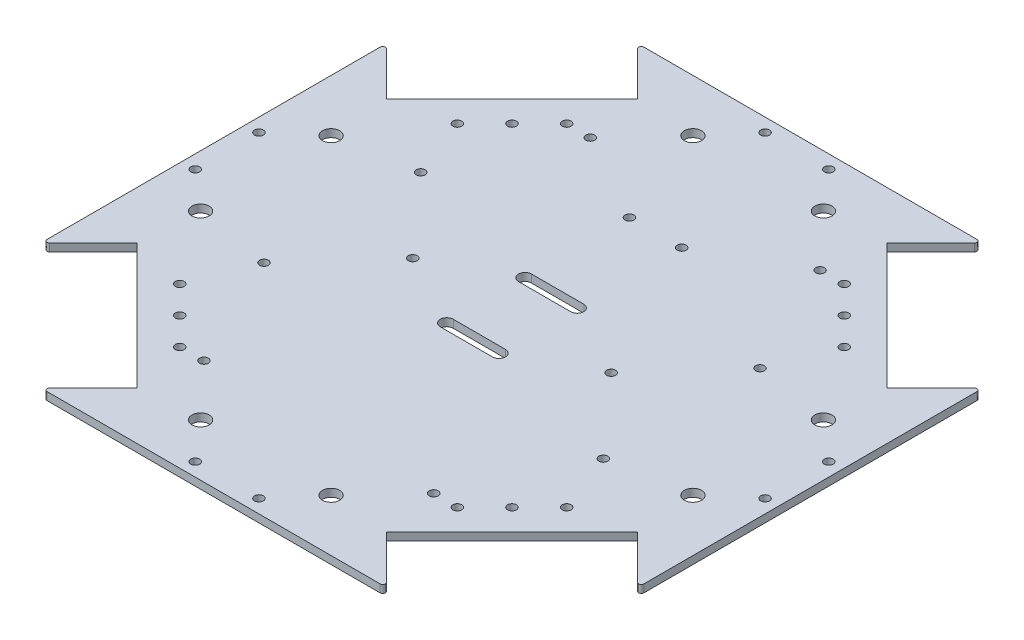
SolidWorks part; units mm, degrees
ref_plane "Front Plane" through (0, 0, 0) normal (0, 0, 1) x (1, 0, 0)
ref_plane "Top Plane" through (0, 0, 0) normal (0, 1, 0) x (1, 0, 0)
ref_plane "Right Plane" through (0, 0, 0) normal (1, 0, 0) x (0, 0, -1)
sketch "Sketch1" plane through (0, 0, 0) normal (0, 1, 0) x (1, 0, 0)
  line L1 (-114.3, 114.3) -> (114.3, 114.3)
  line L2 (-114.3, 114.3) -> (-114.3, -114.3)
  line L3 (-114.3, -114.3) -> (114.3, -114.3)
  line L4 (114.3, 114.3) -> (114.3, -114.3)
  line L5 (-114.3, 114.3) -> (114.3, -114.3) construction
  line L6 (-114.3, -114.3) -> (114.3, 114.3) construction
  point P0 (0, 0)
  dimension "D1" = 228.6
  dimension "D2" = 228.6
extrude "plate" add sketch "Sketch1" along normal blind 3
sketch "Sketch8" plane through (0, 3, 0) normal (0, 1, 0) x (1, 0, 0)
  line L0 (-114.3, 114.3) -> (114.3, -114.3) construction
  line L1 (114.3, 114.3) -> (-114.3, -114.3) construction
  line L2 (-50.6604, 177.9396) -> (177.9396, -50.6604) construction
  line L3 (0, 0) -> (63.6396, 63.6396) construction
  circle A0 centre (63.6396, 63.6396) radius 1.7
  circle A1 centre (74.1048, 53.1744) radius 1.7
  circle A2 centre (53.1744, 74.1048) radius 1.7
  circle A3 centre (63.6396, -63.6396) radius 1.7
  circle A4 centre (74.1048, -53.1744) radius 1.7
  circle A5 centre (53.1744, -74.1048) radius 1.7
  circle A6 centre (-63.6396, -63.6396) radius 1.7
  circle A7 centre (-53.1744, -74.1048) radius 1.7
  circle A8 centre (-74.1048, -53.1744) radius 1.7
  circle A9 centre (-63.6396, 63.6396) radius 1.7
  circle A10 centre (-74.1048, 53.1744) radius 1.7
  circle A11 centre (-53.1744, 74.1048) radius 1.7
  dimension "D2" = 3.4
  dimension "D3" = 3.4
  dimension "D4" = 3.4
  dimension "D5" = 14.8
  dimension "D6" = 14.8
  dimension "D8" = 90
  dimension "D9" = 90
  dimension "D1" = 90
  dimension "D7" = 4
extrude "motor-mount-holes" cut sketch "Sketch8" against normal blind 3
sketch "Sketch9" plane through (0, 3, 0) normal (0, 1, 0) x (1, 0, 0)
  line L0 (0, -114.3) -> (0, 114.3) construction
  line L1 (-38, 0) -> (38, 0) construction
  line L4 (114.3, 114.3) -> (-114.3, 114.3) construction
  line L5 (-114.3, -114.3) -> (114.3, -114.3) construction
  circle A0 centre (-38, 0) radius 1.7
  circle A1 centre (38, 0) radius 1.7
  point P3 (0, 0)
  dimension "D3" = 3.4
  dimension "D2" = 38
extrude "connector-board-holes" cut sketch "Sketch9" against normal blind 3
sketch "Sketch11" plane through (0, 3, 0) normal (0, 1, 0) x (1, 0, 0)
  line L0 (-114.3, 0) -> (114.3, 0) construction
  line L1 (-114.3, 55) -> (114.3, 55) construction
  line L2 (0, -114.3) -> (0, 114.3) construction
  line L3 (27.5, -114.3) -> (27.5, 114.3) construction
  line L4 (-27.5, -114.3) -> (-27.5, 114.3) construction
  line L5 (-123.5172, 0) -> (114.3, 0) construction
  line L6 (-114.3, 114.3) -> (-114.3, -114.3) construction
  line L7 (114.3, -114.3) -> (114.3, 114.3) construction
  line L8 (0, -94.2235) -> (0, 114.3) construction
  line L9 (114.3, 114.3) -> (-114.3, 114.3) construction
  line L10 (-114.3, -114.3) -> (114.3, -114.3) construction
  line L11 (-123.5172, 55) -> (114.3, 55) construction
  line L12 (-27.5, -94.2235) -> (-27.5, 114.3) construction
  line L13 (27.5, -94.2235) -> (27.5, 114.3) construction
  circle A0 centre (-10, 55) radius 1.7
  circle A1 centre (10, 55) radius 1.7
  dimension "D4" = 3.4
  dimension "D5" = 3.4
  dimension "D6" = 10
  dimension "D7" = 20
  dimension "D1" = 55
  dimension "D2" = 27.5
  dimension "D3" = 27.5
extrude "motor-controller-holder-arduino-holes" cut sketch "Sketch11" against normal up to next
sketch "Sketch12" plane through (0, 3, 0) normal (0, 1, 0) x (1, 0, 0)
  line L0 (114.3, 0) -> (-114.3, 0) construction
  line L1 (114.3, -114.3) -> (114.3, 114.3) construction
  line L2 (-114.3, 114.3) -> (-114.3, -114.3) construction
  line L3 (-10, 15) -> (10, 15) construction
  line L4 (-10, 17.5) -> (10, 17.5)
  line L5 (-10, 12.5) -> (10, 12.5)
  line L6 (-10, -15) -> (10, -15) construction
  line L7 (-10, -12.5) -> (10, -12.5)
  line L8 (-10, -17.5) -> (10, -17.5)
  line L9 (0, 114.3) -> (0, -114.3) construction
  line L10 (114.3, 114.3) -> (-114.3, 114.3) construction
  line L11 (-114.3, -114.3) -> (114.3, -114.3) construction
  arc A0 (-10, 17.5) -> (-10, 12.5) centre (-10, 15) ccw
  arc A1 (10, 12.5) -> (10, 17.5) centre (10, 15) ccw
  arc A2 (-10, -12.5) -> (-10, -17.5) centre (-10, -15) ccw
  arc A3 (10, -17.5) -> (10, -12.5) centre (10, -15) ccw
  point P8 (0, 15)
  point P13 (0, -15)
  dimension "D5" = 2.5
  dimension "D6" = 2.5
  dimension "D1" = 15
  dimension "D2" = 15
  dimension "D3" = 20
  dimension "D4" = 20
extrude "cable-slots" cut sketch "Sketch12" against normal up to next
sketch "Sketch13" plane through (0, 3, 0) normal (0, 1, 0) x (1, 0, 0)
  line L0 (0, -114.3) -> (0, 114.3) construction
  line L1 (-114.3, -114.3) -> (114.3, -114.3) construction
  line L2 (114.3, 114.3) -> (-114.3, 114.3) construction
  line L3 (-114.3, 109.1438) -> (114.3, 109.1438) construction
  line L4 (-114.3, 114.3) -> (-114.3, -114.3) construction
  line L5 (114.3, -114.3) -> (114.3, 114.3) construction
  line L6 (0, 0) -> (12.2, 109.1438) construction
  circle A0 centre (-12.2, 109.1438) radius 1.7
  circle A1 centre (12.2, 109.1438) radius 1.7
  circle A14 centre (109.1438, -12.2) radius 1.7
  circle A15 centre (109.1438, 12.2) radius 1.7
  circle A16 centre (-12.2, -109.1438) radius 1.7
  circle A17 centre (12.2, -109.1438) radius 1.7
  circle A18 centre (-109.1438, 12.2) radius 1.7
  circle A19 centre (-109.1438, -12.2) radius 1.7
  dimension "D2" = 3.4
  dimension "D3" = 3.4
  dimension "D1" = 5.1562
  dimension "D4" = 12.2
  dimension "D5" = 12.2
  dimension "D7" = 109.8235
  dimension "D8" = 6.378
  dimension "D6" = 4
extrude "wall-bracket-holes" cut sketch "Sketch13" against normal up to next
sketch "Sketch14" plane through (0, 3, 0) normal (0, 1, 0) x (1, 0, 0)
  line L0 (-114.3, 0) -> (114.3, 0) construction
  line L1 (-114.3, 114.3) -> (-114.3, -114.3) construction
  line L2 (114.3, -114.3) -> (114.3, 114.3) construction
  line L4 (0, 114.3) -> (0, -114.3) construction
  line L5 (114.3, 114.3) -> (-114.3, 114.3) construction
  line L6 (-114.3, -114.3) -> (114.3, -114.3) construction
  line L7 (-65, 30) -> (-65, -30) construction
  circle A8 centre (-65, 30) radius 1.7
  circle A9 centre (-65, -30) radius 1.7
  circle A10 centre (65, -30) radius 1.7
  circle A11 centre (65, 30) radius 1.7
  point P26 (-65, 0)
  dimension "D6" = 3.4
  dimension "D7" = 30
  dimension "D8" = 65
extrude "battery-holder-holes" cut sketch "Sketch14" against normal up to next
sketch "Sketch15" plane through (0, 3, 0) normal (0, 1, 0) x (1, 0, 0)
  line L0 (114.3, 0) -> (-114.3, 0) construction
  line L1 (114.3, -114.3) -> (114.3, 114.3) construction
  line L2 (-114.3, 114.3) -> (-114.3, -114.3) construction
  line L3 (114.3, 114.3) -> (-114.3, 114.3) construction
  line L4 (-25, 94.3) -> (25, 94.3) construction
  line L5 (-25, -94.3) -> (25, -94.3) construction
  line L6 (-114.3, -114.3) -> (114.3, -114.3) construction
  line L8 (0, 94.3) -> (0, 114.3) construction
  circle A0 centre (-94.3, 25) radius 3.3
  circle A1 centre (-94.3, -25) radius 3.3
  circle A2 centre (94.3, 25) radius 3.3
  circle A3 centre (94.3, -25) radius 3.3
  circle A4 centre (25, 94.3) radius 3.3
  circle A5 centre (-25, 94.3) radius 3.3
  circle A6 centre (25, -94.3) radius 3.3
  circle A7 centre (-25, -94.3) radius 3.3
  point P25 (0, 0)
  dimension "D3" = 6.6
  dimension "D4" = 6.6
  dimension "D6" = 6.6
  dimension "D7" = 6.6
  dimension "D13" = 20
  dimension "D1" = 50
  dimension "D2" = 25
  dimension "D5" = 20
  dimension "D8" = 25
  dimension "D9" = 50
  dimension "D10" = 20
  dimension "D12" = 20
  dimension "D11" = 2
extrude "load-mount-holes" cut sketch "Sketch15" against normal up to next
sketch "Sketch10" plane through (0, 3, 0) normal (0, 1, 0) x (1, 0, 0)
  line L0 (0, 114.3) -> (0, -114.3) construction
  line L1 (114.3, 114.3) -> (-114.3, 114.3) construction
  line L2 (-114.3, -114.3) -> (114.3, -114.3) construction
  line L3 (-114.3, 0) -> (114.3, 0) construction
  line L4 (-114.3, 114.3) -> (-114.3, -114.3) construction
  line L5 (114.3, -114.3) -> (114.3, 114.3) construction
  line L6 (44, 74) -> (-44, 74) construction
  line L7 (-44, 74) -> (-44, -74) construction
  circle A5 centre (44, 74) radius 1.7
  circle A6 centre (44, -74) radius 1.7
  circle A7 centre (-44, -74) radius 1.7
  circle A8 centre (-44, 74) radius 1.7
  point P20 (0, 74)
  point P21 (-44, 0)
  dimension "D1" = 3.4
  dimension "D2" = 44
  dimension "D3" = 74
extrude "level2-standoff-holes" cut sketch "Sketch10" against normal up to next
sketch "Sketch2" plane through (0, 3, 0) normal (0, 1, 0) x (1, 0, 0)
  line L0 (-114.3, -114.3) -> (114.3, 114.3) construction
  line L1 (114.3, -114.3) -> (-114.3, 114.3) construction
  line L2 (-90.2584, -138.3416) -> (138.3416, 90.2584) construction
  line L3 (-138.3416, -90.2584) -> (90.2584, 138.3416) construction
  line L4 (186.142, -42.458) -> (-42.458, 186.142) construction
  line L5 (114.3, 114.3) -> (66.2167, 114.3)
  line L6 (114.3, 114.3) -> (-114.3, 114.3) construction
  line L7 (66.2167, 114.3) -> (47.8004, 95.8837)
  line L8 (47.8004, 95.8837) -> (95.8837, 47.8004)
  line L9 (95.8837, 47.8004) -> (114.3, 66.2167)
  line L10 (114.3, 66.2167) -> (114.3, 114.3)
  line L41 (66.2167, -114.3) -> (114.3, -114.3)
  line L42 (114.3, -114.3) -> (114.3, -66.2167)
  line L43 (114.3, -66.2167) -> (95.8837, -47.8004)
  line L44 (95.8837, -47.8004) -> (47.8004, -95.8837)
  line L45 (47.8004, -95.8837) -> (66.2167, -114.3)
  line L46 (-114.3, -66.2167) -> (-114.3, -114.3)
  line L47 (-114.3, -114.3) -> (-66.2167, -114.3)
  line L48 (-66.2167, -114.3) -> (-47.8004, -95.8837)
  line L49 (-47.8004, -95.8837) -> (-95.8837, -47.8004)
  line L50 (-95.8837, -47.8004) -> (-114.3, -66.2167)
  line L51 (-66.2167, 114.3) -> (-114.3, 114.3)
  line L52 (-114.3, 114.3) -> (-114.3, 66.2167)
  line L53 (-114.3, 66.2167) -> (-95.8837, 47.8004)
  line L54 (-95.8837, 47.8004) -> (-47.8004, 95.8837)
  line L55 (-47.8004, 95.8837) -> (-66.2167, 114.3)
  line L56 (0, 0) -> (95.8837, 47.8004) construction
  dimension "D5" = 107.138
  dimension "D6" = 18.503
  dimension "D1" = 34
  dimension "D2" = 34
  dimension "D3" = 101.6
  dimension "D4" = 4
extrude "wheel-slots" cut sketch "Sketch2" against normal blind 3
fillet "Fillet1" radius 1 8 edges at (66.2167, 1.5, -114.3) (114.3, 1.5, -66.2167) (114.3, 1.5, 66.2167) (-66.2167, 1.5, -114.3) (-114.3, 1.5, -66.2167) (-114.3, 1.5, 66.2167) (-66.2167, 1.5, 114.3) (66.2167, 1.5, 114.3)
